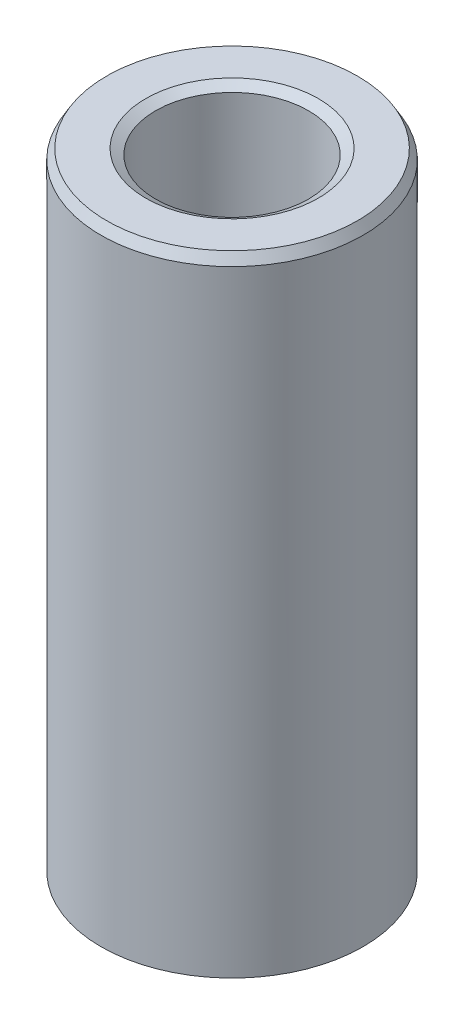
SolidWorks part; units mm, degrees
ref_plane "Front Plane" through (0, 0, 0) normal (0, 0, 1) x (1, 0, 0)
ref_plane "Top Plane" through (0, 0, 0) normal (0, 1, 0) x (1, 0, 0)
ref_plane "Right Plane" through (0, 0, 0) normal (1, 0, 0) x (0, 0, -1)
sketch "Sketch1" plane through (0, 0, 0) normal (0, 1, 0) x (1, 0, 0)
  circle A0 centre (0, 0) radius 12.5
  dimension "SLEEVE_OD" = 25
extrude "Boss-Extrude1" add sketch "Sketch1" along normal blind 60.2453
sketch "Sketch2" plane through (0, 0, 0) normal (0, 1, 0) x (1, 0, 0)
  circle A0 centre (0, 0) radius 7.3008
  dimension "BORE_D" = 14.6016
extrude "Cut-Extrude1" cut sketch "Sketch2" along normal through all
chamfer "Chamfer1" distance 0.9334 angle 30 4 edges at (0, 60.2453, 7.3008) (0, 0, 7.3008) (0, 0, 12.5) (0, 60.2453, 12.5) first distance on face at (0, 60.2453, 7.3008) first distance on face at (0, 0, 7.3008) first distance on face at (0, 60.2453, 12.5)
